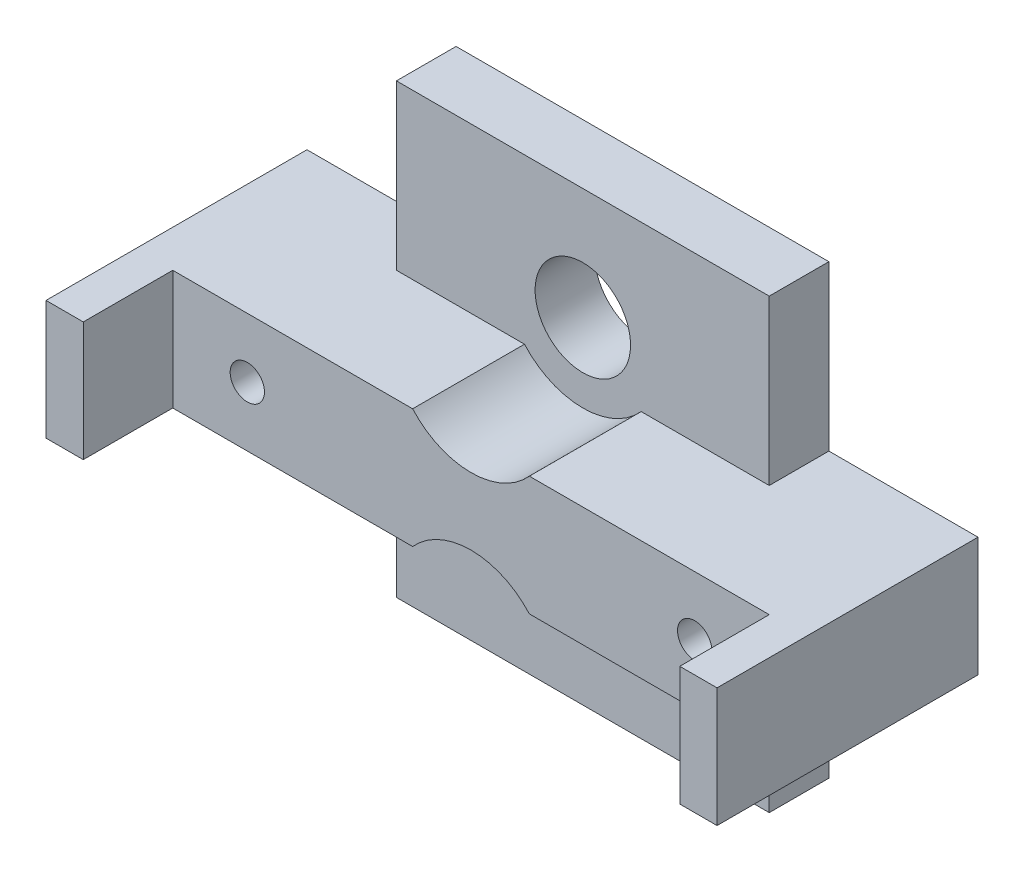
SolidWorks part; units mm, degrees
ref_plane "정면" through (0, 0, 0) normal (0, 0, 1) x (1, 0, 0)
ref_plane "윗면" through (0, 0, 0) normal (0, 1, 0) x (1, 0, 0)
ref_plane "우측면" through (0, 0, 0) normal (1, 0, 0) x (0, 0, -1)
sketch "스케치1" plane through (0, 0, 0) normal (0, 0, 1) x (1, 0, 0)
  line L1 (-12.5, 15) -> (12.5, 15)
  line L2 (-12.5, 15) -> (-12.5, -15)
  line L3 (-12.5, -15) -> (12.5, -15)
  line L4 (12.5, 15) -> (12.5, -15)
  circle A0 centre (0, 7.5) radius 3.2
  circle A1 centre (0, -7.5) radius 3.2
  point P10 (0, 15)
  point P11 (12.5, 0)
  dimension "D3" = 6.4
  dimension "D4" = 6.4
  dimension "D1" = 30
  dimension "D2" = 25
  dimension "D5" = 15
  dimension "D6" = 7.5
extrude "보스-돌출1" add sketch "스케치1" along normal blind 4
sketch "스케치2" plane through (0, 0, 4) normal (0, 0, 1) x (1, 0, 0)
  line L1 (-20, 4) -> (20, 4)
  line L2 (-20, 4) -> (-20, -4)
  line L3 (-20, -4) -> (20, -4)
  line L4 (20, 4) -> (20, -4)
  circle A1 centre (15, 0) radius 1.15
  circle A2 centre (-15, 0) radius 1.15
  point P11 (-20, 0)
  dimension "D5" = 2.3
  dimension "D1" = 8
  dimension "D2" = 40
  dimension "D3" = 20
  dimension "D4" = 4
  dimension "D6" = 15
  dimension "D7" = 15
extrude "보스-돌출2" add sketch "스케치2" against normal up to surface (4 mm away) and the other way blind 7.5 up to face at (0, 0, 0)
sketch "스케치4" plane through (0, 0, 0) normal (0, 0, -1) x (-1, 0, 0)
  line L7 (17.4826, 0) -> (16.2413, 2.15)
  line L8 (16.2413, 2.15) -> (13.7587, 2.15)
  line L9 (13.7587, 2.15) -> (12.5174, 0)
  line L10 (12.5174, 0) -> (13.7587, -2.15)
  line L11 (13.7587, -2.15) -> (16.2413, -2.15)
  line L12 (16.2413, -2.15) -> (17.4826, 0)
  line L13 (-12.5174, 0) -> (-13.7587, 2.15)
  line L14 (-13.7587, 2.15) -> (-16.2413, 2.15)
  line L15 (-16.2413, 2.15) -> (-17.4826, 0)
  line L16 (-17.4826, 0) -> (-16.2413, -2.15)
  line L17 (-16.2413, -2.15) -> (-13.7587, -2.15)
  line L18 (-13.7587, -2.15) -> (-12.5174, 0)
  circle A1 centre (15, 0) radius 2.15 construction
  circle A2 centre (-15, 0) radius 2.15 construction
  dimension "D2" = 4.3
  dimension "D3" = 4.3
extrude "컷-돌출2" cut sketch "스케치4" against normal blind 9.5
sketch "스케치5" plane through (0, 0, 4) normal (0, 0, 1) x (1, 0, 0)
  circle A0 centre (0, 7.5) radius 5.25
  circle A1 centre (0, -7.5) radius 5.25
  circle A2 centre (0, -7.5) radius 3.2 construction
  dimension "D1" = 10.5
extrude "컷-돌출3" cut sketch "스케치5" along normal up to surface (7.5 mm away) up to face at (16.15, 0, 11.5)
sketch "스케치6" plane through (0, 0, 0) normal (0, 0, -1) x (-1, 0, 0)
  line L0 (-20, -4) -> (-12.5, -4) construction
  line L1 (20, 4) -> (22.5, 4)
  line L2 (20, 4) -> (20, -4)
  line L3 (20, -4) -> (22.5, -4)
  line L4 (22.5, 4) -> (22.5, -4)
  line L5 (-20, 4) -> (-22.5, 4)
  line L6 (-20, 4) -> (-20, -4)
  line L7 (-20, -4) -> (-22.5, -4)
  line L8 (-22.5, 4) -> (-22.5, -4)
  line L9 (12.5, -4) -> (20, -4) construction
  dimension "D1" = 2.5
extrude "보스-돌출3" add sketch "스케치6" against normal blind 17.5
